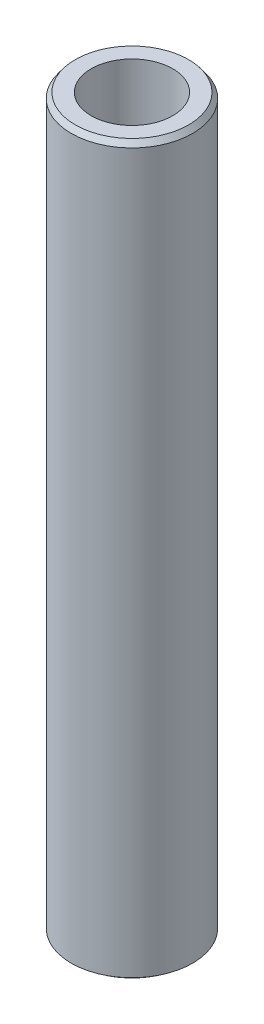
SolidWorks part; units mm, degrees
ref_plane "Front Plane" through (0, 0, 0) normal (0, 0, 1) x (1, 0, 0)
ref_plane "Top Plane" through (0, 0, 0) normal (0, 1, 0) x (1, 0, 0)
ref_plane "Right Plane" through (0, 0, 0) normal (1, 0, 0) x (0, 0, -1)
sketch "Sketch1" plane through (0, 0, 0) normal (0, 1, 0) x (1, 0, 0)
  circle A0 centre (0, 0) radius 50
  dimension "SHAFT_OD" = 100
extrude "Boss-Extrude1" add sketch "Sketch1" along normal blind 600
sketch "Sketch2" plane through (0, 0, 0) normal (0, 1, 0) x (1, 0, 0)
  circle A0 centre (0, 0) radius 33.6064
  dimension "BORE_D" = 67.2127
extrude "Cut-Extrude1" cut sketch "Sketch2" along normal through all
chamfer "Chamfer1" distance 4.4256 angle 36.934 2 edges at (0, 600, 50) (0, 0, 50) first distance on face at (0, 600, 50) first distance on face at (0, 0, 33.6064)
